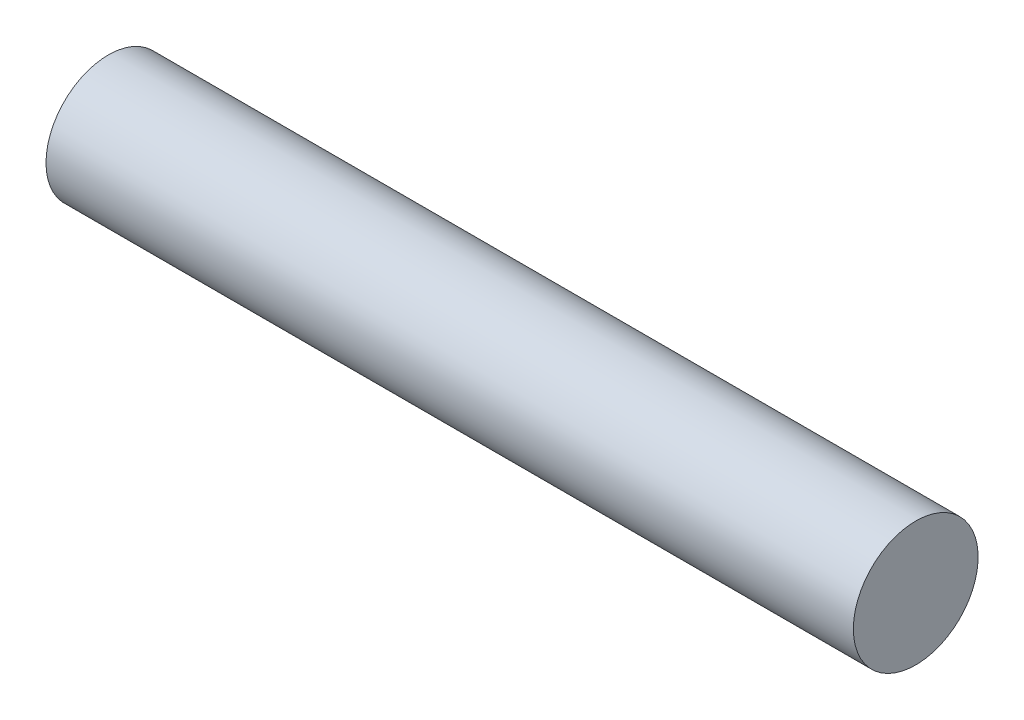
SolidWorks part; units mm, degrees
material "Chrome Stainless Steel"
ref_plane "Front Plane" through (0, 0, 0) normal (0, 0, 1) x (1, 0, 0)
ref_plane "Top Plane" through (0, 0, 0) normal (0, 1, 0) x (1, 0, 0)
ref_plane "Right Plane" through (0, 0, 0) normal (1, 0, 0) x (0, 0, -1)
ref_axis "X-axis" through (-88.99, 0, 0) along (1, 0, 0)
ref_axis "Y-axis" through (0, -55, 0) along (0, 1, 0)
ref_axis "Z-axis" through (0, 0, 55) along (0, 0, -1)
sketch "Sketch1" plane through (0, 0, 0) normal (0, 0, 1) x (1, 0, 0)
  line L0 (-5.8278, 0) -> (32.1971, 0) construction
  line L1 (0, 0) -> (25.4762, 0)
  line L2 (0, 0) -> (0, 1.9685)
  line L3 (0, 1.9685) -> (25.4762, 1.9685)
  line L4 (25.4762, 0) -> (25.4762, 1.9685)
  dimension "D1" = 25.4762
  dimension "D2" = 3.937
revolve "Revolve1" add sketch "Sketch1" angle 360 about L0
